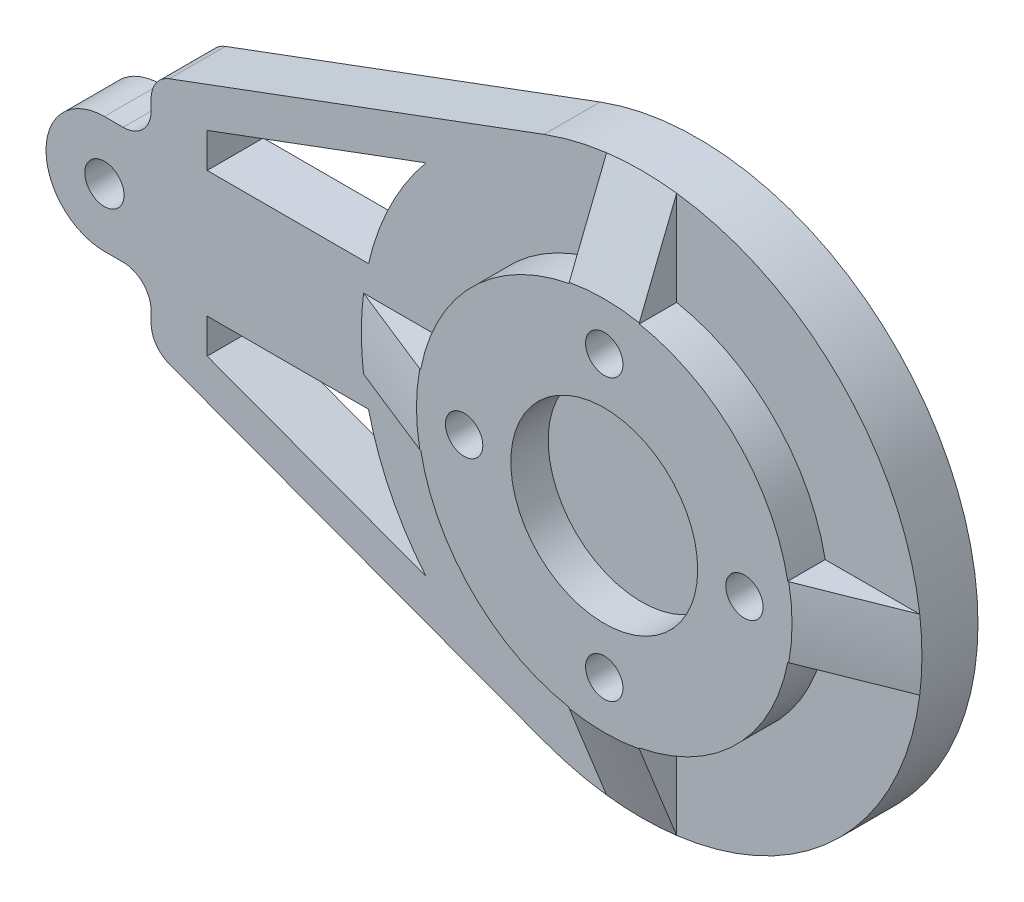
SolidWorks part; units mm, degrees
ref_plane "Front Plane" through (0, 0, 0) normal (0, 0, 1) x (1, 0, 0)
ref_plane "Top Plane" through (0, 0, 0) normal (0, 1, 0) x (1, 0, 0)
ref_plane "Right Plane" through (0, 0, 0) normal (1, 0, 0) x (0, 0, -1)
sketch "Sketch2" plane through (0, 0, 0) normal (0, 0, 1) x (1, 0, 0)
  circle A0 centre (0, 0) radius 20
  circle A1 centre (0, 0) radius 40
  dimension "D1" = 40
  dimension "D2" = 80
extrude "Boss-Extrude1" add sketch "Sketch2" along normal blind 8
sketch "Sketch3" plane through (0, 0, 0) normal (0, 0, -1) x (-1, 0, 0)
  line L0 (0, 0) -> (105, 0) construction
  line L1 (105, -25) -> (105, 25)
  line L2 (105, 25) -> (20.8942, 56.2444)
  line L3 (105, -25) -> (20.8942, -56.2444)
  arc A0 (20.8942, 56.2444) -> (20.8942, -56.2444) centre (0, 0) ccw
  point P7 (105, 0)
  dimension "D1" = 120
  dimension "D2" = 105
  dimension "D3" = 50
extrude "Boss-Extrude2" add sketch "Sketch3" along normal blind 12
sketch "Sketch4" plane through (0, 0, -12) normal (0, 0, -1) x (-1, 0, 0)
  line L0 (0, 0) -> (0, 30) construction
  circle A0 centre (0, 30) radius 7.5
  circle A1 centre (30, 0) radius 7.5
  circle A2 centre (0, -30) radius 7.5
  circle A3 centre (-30, 0) radius 7.5
  point P13 (0, 0)
  dimension "D2" = 15
  dimension "D1" = 30
  dimension "D3" = 4
extrude "Cut-Extrude1" cut sketch "Sketch4" against normal blind 10
sketch "Sketch5" plane through (0, 0, -2) normal (0, 0, -1) x (-1, 0, 0)
  circle A0 centre (30, 0) radius 4
  circle A1 centre (0, -30) radius 4
  circle A2 centre (-30, 0) radius 4
  circle A3 centre (0, 30) radius 4
  point P12 (0, 0)
  dimension "D1" = 8
  dimension "D2" = 4
extrude "Cut-Extrude2" cut sketch "Sketch5" against normal blind 29
sketch "Sketch6" plane through (0, 0, 0) normal (0, 0, 1) x (1, 0, 0)
  line L0 (39.2906, -7.5) -> (59.5294, -7.5)
  line L1 (39.2906, 7.5) -> (59.5294, 7.5)
  line L2 (-7.5, 39.2906) -> (-7.5, 59.5294)
  line L3 (7.5, 39.2906) -> (7.5, 59.5294)
  line L4 (-7.5, -39.2906) -> (-7.5, -59.5294)
  line L5 (7.5, -39.2906) -> (7.5, -59.5294)
  line L6 (-39.2906, 7.5) -> (-59.5294, 7.5)
  line L7 (-39.2906, -7.5) -> (-59.5294, -7.5)
  arc A1 (7.5, 39.2906) -> (-7.5, 39.2906) centre (0, 0) ccw
  arc A5 (7.5, 59.5294) -> (-7.5, 59.5294) centre (0, 0) ccw
  arc A6 (59.5294, -7.5) -> (59.5294, 7.5) centre (0, 0) ccw
  arc A7 (39.2906, -7.5) -> (39.2906, 7.5) centre (0, 0) ccw
  arc A8 (-7.5, -59.5294) -> (7.5, -59.5294) centre (0, 0) ccw
  arc A9 (-7.5, -39.2906) -> (7.5, -39.2906) centre (0, 0) ccw
  arc A10 (-59.5294, 7.5) -> (-59.5294, -7.5) centre (0, 0) ccw
  arc A11 (-39.2906, 7.5) -> (-39.2906, -7.5) centre (0, 0) ccw
  point P10 (0, 48.2861)
  point P13 (-7.5, 49.41)
  point P16 (7.5, 49.41)
  point P25 (0, 0)
  dimension "D1" = 15
  dimension "D2" = 4
extrude "Boss-Extrude3" add sketch "Sketch6" along direction (0, 0, 1) on the side of the normal blind 8
chamfer "Chamfer3" distance 8 angle 68 4 edges at (0, 60, 8) (60, 0, 8) (-60, 0, 8) (0, -60, 8) first distance on face at (15.8462, 0, 1.5) first distance on face at (-59.7647, 0, 4)
sketch "Sketch7" plane through (0, 0, -12) normal (0, 0, -1) x (-1, 0, 0)
  line L0 (105, 0) -> (115, 0) construction
  line L1 (105, -25) -> (105, 25) construction
  line L2 (115, 12.5) -> (105, 12.5)
  line L3 (105, 12.5) -> (105, -12.5)
  line L4 (105, -12.5) -> (115, -12.5)
  arc A0 (115, -12.5) -> (115, 12.5) centre (115, 0) ccw
  dimension "D2" = 25
  dimension "D1" = 10
extrude "Boss-Extrude4" add sketch "Sketch7" against normal up to surface (12 mm away) up to face at (-40.8222, 0, 0)
fillet "Fillet1" radius 6 4 edges at (-105, 25, -6) (-105, 12.5, -6) (-105, -25, -6) (-105, -12.5, -6)
sketch "Sketch8" plane through (0, 0, -12) normal (0, 0, -1) x (-1, 0, 0)
  line L1 (118.7786, 6.485) -> (111.2731, 6.5149)
  line L2 (111.2731, 6.5149) -> (107.4945, 0.0298)
  line L3 (107.4945, 0.0298) -> (111.2214, -6.485)
  line L4 (111.2214, -6.485) -> (118.7269, -6.5149)
  line L5 (118.7269, -6.5149) -> (122.5055, -0.0298)
  line L6 (122.5055, -0.0298) -> (118.7786, 6.485)
  circle A0 centre (115, 0) radius 6.5 construction
  dimension "D1" = 13
extrude "Cut-Extrude3" cut sketch "Sketch8" against normal blind 6
sketch "Sketch9" plane through (0, 0, -6) normal (0, 0, -1) x (-1, 0, 0)
  circle A0 centre (115, 0) radius 4.2
  dimension "D1" = 8.4
extrude "Cut-Extrude4" cut sketch "Sketch9" against normal blind 6
sketch "Sketch10" plane through (0, 0, 0) normal (0, 0, 1) x (1, 0, 0)
  line L2 (-20.8942, -56.2444) -> (-101.0894, -26.4527) construction
  line L3 (-58.4615, -13.5) -> (-93, -13.5)
  line L4 (-59.5294, -7.5) -> (-39.2906, -7.5) construction
  line L6 (-93, -13.5) -> (-93, -20.9237)
  line L7 (-60, 0) -> (-127.5, 0) construction
  line L9 (-93, 20.9237) -> (-46.1679, 38.3213)
  line L10 (-93, 13.5) -> (-93, 20.9237)
  line L11 (-93, -20.9237) -> (-46.1679, -38.3213)
  line L12 (-58.4615, 13.5) -> (-93, 13.5)
  arc A0 (-58.4615, -13.5) -> (-46.1679, -38.3213) centre (0, 0) ccw
  arc A2 (-59.5294, 7.5) -> (-59.5294, -7.5) centre (0, 0) ccw construction
  arc A3 (-115, 12.5) -> (-115, -12.5) centre (-115, 0) ccw construction
  arc A4 (-58.4615, 13.5) -> (-46.1679, 38.3213) centre (0, 0) cw
  dimension "D1" = 60
  dimension "D3" = 8
  dimension "D4" = 6
extrude "Cut-Extrude5" cut sketch "Sketch10" against normal blind 22
